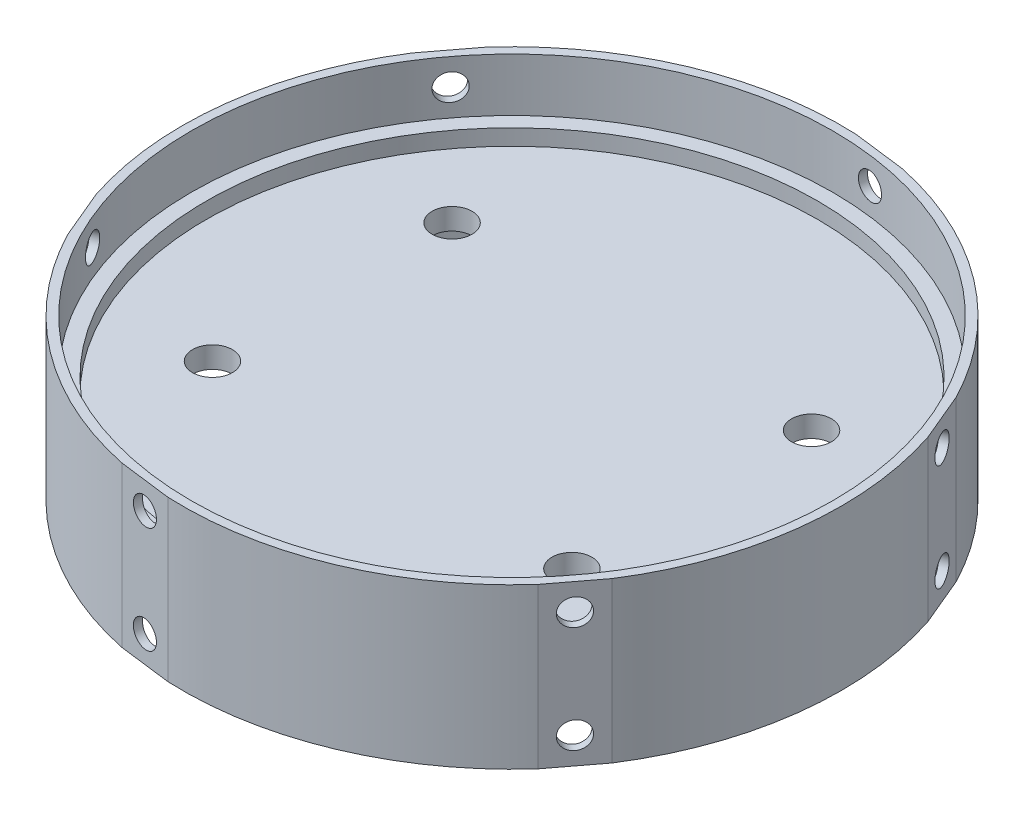
SolidWorks part; units mm, degrees
material "6061-T6 (SS)"
ref_plane "Front Plane" through (0, 0, 0) normal (0, 0, 1) x (1, 0, 0)
ref_plane "Top Plane" through (0, 0, 0) normal (0, 1, 0) x (1, 0, 0)
ref_plane "Right Plane" through (0, 0, 0) normal (1, 0, 0) x (0, 0, -1)
ref_axis "Axis1" through (0, 55, 0) along (0, -1, 0)
sketch "Sketch3" plane through (0, 0, 0) normal (0, 1, 0) x (1, 0, 0)
  circle A0 centre (0, 0) radius 78.5876
  dimension "D1" = 157.1752
extrude "Boss-Extrude1" add sketch "Sketch3" along normal blind 2.54 and the other way blind 2.54
sketch "Sketch4" plane through (0, 2.54, 0) normal (0, 1, 0) x (1, 0, 0)
  circle A0 centre (0, 0) radius 78.5876
  circle A1 centre (0, 0) radius 72.8662
  dimension "D1" = 157.1752
  dimension "D2" = 145.7325
extrude "Boss-Extrude3" add sketch "Sketch4" along normal blind 3.81
sketch "Sketch6" plane through (0, 6.35, 0) normal (0, 1, 0) x (1, 0, 0)
  circle A0 centre (0, 0) radius 78.5876
  circle A1 centre (0, 0) radius 76.454
  dimension "D1" = 157.1752
  dimension "D2" = 152.908
extrude "Boss-Extrude4" add sketch "Sketch6" along normal blind 12.7
hole_wizard "1/4 (0.25) Diameter Hole2" positions "3DSketch2" profile "Sketch7" hole size "1/4" standard "ANSI Inch" end condition up to next
sketch3d "3DSketch2"
  point P0 (-9.8633, 12.7, 77.9662)
  dimension "D1" = 6.35
sketch "Sketch7" plane through (-9.8633, 12.7, 77.9662) normal (0, 1, 0) x (0.9921, 0, 0.1255)
  line L0 (0, 0) -> (0, 185.7135)
  line L1 (0, 185.7135) -> (3.175, 185.7135)
  line L2 (3.175, 185.7135) -> (3.175, 0)
  line L5 (3.175, 0) -> (0, 0)
  line L11 (0, -6.35) -> (0, 107.95) construction
  dimension "Thru Hole Dia." = 6.35
  dimension "Thru Hole Depth" = 185.7135
pattern_circular "CirPattern2" count 6 over 360 about axis through (0, 55, 0) along (0, -1, 0) of "1/4 (0.25) Diameter Hole2"
mirror "Mirror3" about plane through (0, 0, 0) normal (0, 1, 0) of "Boss-Extrude3", "Boss-Extrude4", "1/4 (0.25) Diameter Hole2", "CirPattern2"
hole_wizard "3/8 (0.375) Diameter Hole1" positions "Sketch8" profile "Sketch9" hole size "3/8" standard "ANSI Inch" end condition up to next
sketch "Sketch8" plane through (0, 2.54, 0) normal (0, 1, 0) x (1, 0, 0)
  line L0 (-42.8625, 28.575) -> (42.8625, -28.575) construction
  point P0 (-42.8625, 28.575)
  point P2 (42.8625, 28.575)
  point P4 (42.8625, -28.575)
  point P6 (-42.8625, -28.575)
  point P17 (0, 0)
  dimension "D1" = 57.15
  dimension "D2" = 85.725
sketch "Sketch9" plane through (-42.8625, 2.54, -28.575) normal (1, 0, 0) x (0, 0, 1)
  line L0 (0, 0) -> (0, 5.08)
  line L1 (0, 5.08) -> (4.7625, 5.08)
  line L2 (4.7625, 5.08) -> (4.7625, 0)
  line L5 (4.7625, 0) -> (0, 0)
  line L11 (0, -6.35) -> (0, 107.95) construction
  dimension "Thru Hole Dia." = 9.525
  dimension "Thru Hole Depth" = 5.08
ref_axis "Axis2" through (-9.5696, 12.7, 75.645) along (-0.1255, 0, 0.9921)
ref_plane "Plane1" through (-9.8633, 0, 77.9662) normal (-0.1255, 0, 0.9921) x (0.9921, 0, 0.1255)
sketch "Sketch11" plane through (-9.8633, 0, 77.9662) normal (-0.1255, 0, 0.9921) x (0.9921, 0, 0.1255)
  line L1 (-20.18, 23.5914) -> (21.0466, 23.5914)
  line L2 (-20.18, 23.5914) -> (-20.18, -28.7325)
  line L3 (-20.18, -28.7325) -> (21.0466, -28.7325)
  line L4 (21.0466, 23.5914) -> (21.0466, -28.7325)
extrude "Cut-Extrude2" cut sketch "Sketch11" against normal blind 0.254
pattern_circular "CirPattern4" count 6 over 360 about axis through (0, 55, 0) along (0, -1, 0) of "Cut-Extrude2"
